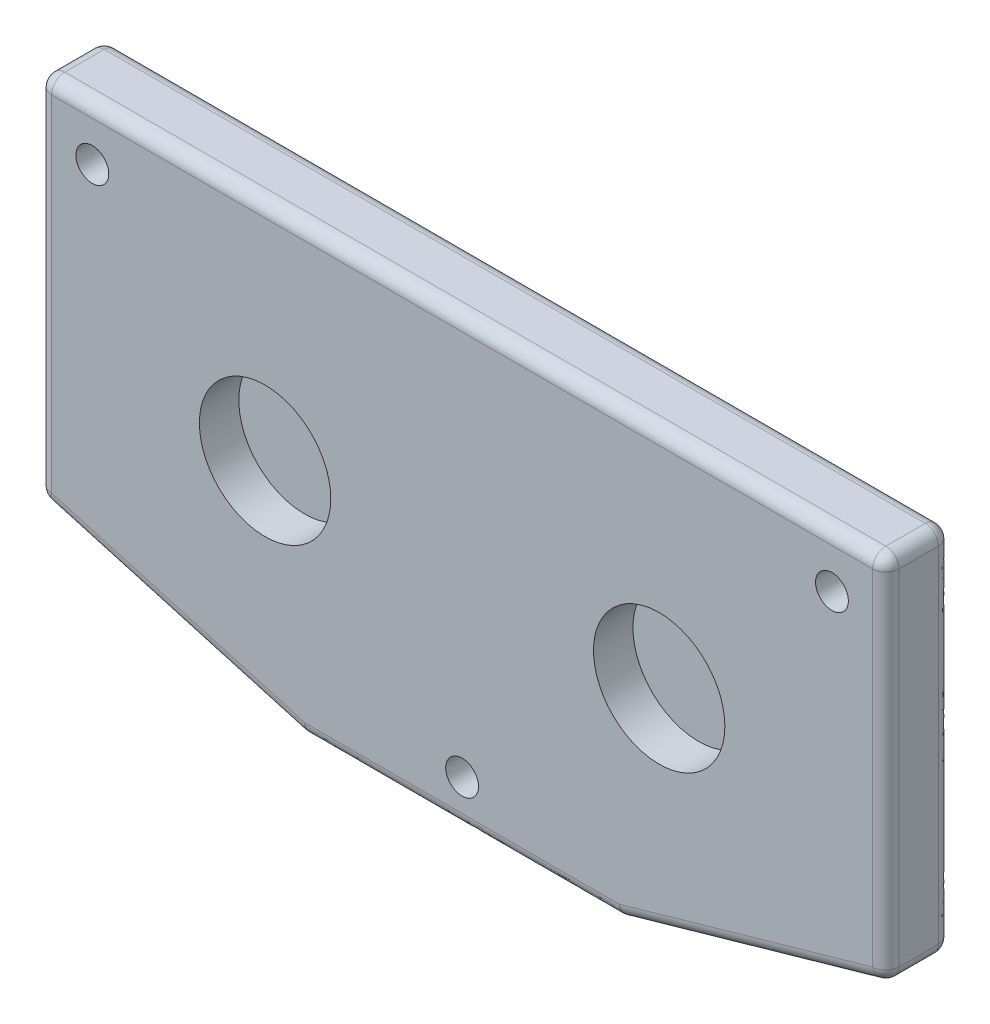
SolidWorks part; units mm, degrees
ref_plane "Front Plane" through (0, 0, 0) normal (0, 0, 1) x (1, 0, 0)
ref_plane "Top Plane" through (0, 0, 0) normal (0, 1, 0) x (1, 0, 0)
ref_plane "Right Plane" through (0, 0, 0) normal (1, 0, 0) x (0, 0, -1)
sketch "Sketch1" plane through (0, 0, 0) normal (0, 0, 1) x (1, 0, 0)
  line L0 (-982.3499, -11) -> (49017.6501, -11) construction
  line L1 (-16.25, 17) -> (46.25, 17)
  line L2 (-17.25, 16) -> (-17.25, -10.2454)
  line L3 (3.0446, -16.75) -> (26.9554, -16.75)
  line L4 (47.25, 16) -> (47.25, -10.2454)
  line L5 (2.7702, -16.7116) -> (-16.5243, -11.207)
  line L6 (46.5243, -11.207) -> (27.2298, -16.7116)
  circle A0 centre (0, 0) radius 5 construction
  circle A1 centre (30, 0) radius 5 construction
  arc A2 (47.25, -10.2454) -> (46.5243, -11.207) centre (46.25, -10.2454) cw
  arc A3 (27.2298, -16.7116) -> (26.9554, -16.75) centre (26.9554, -15.75) cw
  arc A4 (47.25, 16) -> (46.25, 17) centre (46.25, 16) ccw
  arc A5 (-16.25, 17) -> (-17.25, 16) centre (-16.25, 16) ccw
  circle A6 centre (0, 0) radius 17 construction
  circle A7 centre (30, 0) radius 17 construction
  arc A8 (3.0446, -16.75) -> (2.7702, -16.7116) centre (3.0446, -15.75) cw
  arc A9 (-16.5243, -11.207) -> (-17.25, -10.2454) centre (-16.25, -10.2454) cw
  point P11 (47.25, -11)
  point P24 (27.0953, -16.75)
  point P27 (2.9047, -16.75)
  point P30 (-17.25, -11)
  dimension "D1" = 10
  dimension "D4" = 10
  dimension "D8" = 1
  dimension "D9" = 34
  dimension "D11" = 34
  dimension "D12" = 1
  dimension "D2" = 17.25
  dimension "D3" = 16.75
  dimension "D5" = 17.25
  dimension "D6" = 30
  dimension "D7" = 17
  dimension "D10" = 5.75
extrude "Body" add sketch "Sketch1" along normal blind 5
sketch "Sketch2" plane through (0, 0, 5) normal (0, 0, 1) x (1, 0, 0)
  circle A1 centre (0, 0) radius 5
  circle A2 centre (30, 0) radius 5
  dimension "D1" = 10
  dimension "D2" = 10
  dimension "D3" = 30
extrude "LocatingHoles" cut sketch "Sketch2" against normal blind 3
sketch "Sketch3" plane through (0, 0, 0) normal (0, 0, 1) x (1, 0, 0)
  line L0 (15, -1016.75) -> (15, 48983.25) construction
  line L1 (3.0446, -16.75) -> (26.9554, -16.75) construction
  circle A0 centre (15, -13.35) radius 1.25
  circle A1 centre (-13.15, 12.96) radius 1.25
  circle A2 centre (43.15, 12.96) radius 1.25
  point P5 (15, -16.75)
  dimension "D1" = 2.5
  dimension "D3" = 2.5
  dimension "D2" = 3.4
  dimension "D4" = 28.15
  dimension "D5" = 26.31
extrude "ScrewHoles" cut sketch "Sketch3" along normal through all
fillet "VarFillet1" radius 1 2 edges at (15, -16.75, 5) (47.25, 2.8773, 0)
